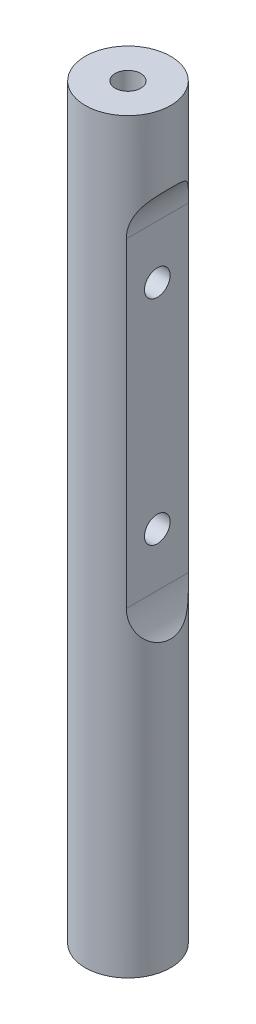
SolidWorks part; units mm, degrees
ref_plane "Front Plane" through (0, 0, 0) normal (0, 0, 1) x (1, 0, 0)
ref_plane "Top Plane" through (0, 0, 0) normal (0, 1, 0) x (1, 0, 0)
ref_plane "Right Plane" through (0, 0, 0) normal (1, 0, 0) x (0, 0, -1)
sketch "Sketch1" plane through (0, 0, 0) normal (0, 1, 0) x (1, 0, 0)
  circle A0 centre (0, 0) radius 5.08
  dimension "D1" = 10.16
extrude "Boss-Extrude1" add sketch "Sketch1" along normal blind 88.9
hole_wizard "Tapped Hole for #4-40 Helicoil1" positions "Sketch2" profile "Sketch4" tap size "#4-40" standard "Helicoil® Inch"
sketch "Sketch2" plane through (0, 88.9, 0) normal (0, 1, 0) x (1, 0, 0)
  point P0 (0, 0)
sketch "Sketch4" plane through (0, 88.9, 0) normal (1, 0, 0) x (0, 0, 1)
  line L0 (0, 0) -> (0, 9.0437)
  line L1 (0, 9.0437) -> (1.524, 8.128)
  line L2 (1.524, 8.128) -> (1.524, 0)
  line L5 (1.524, 0) -> (0, 0)
  line L10 (0, 9.0437) -> (-1.524, 8.128) construction
  line L11 (0, -6.35) -> (0, 107.95) construction
  dimension "Tap Drill Dia." = 3.048
  dimension "Tap Drill Depth" = 8.128
  dimension "Drill Angle" = 118
cosmetic thread "Hole Thread1" parameters "D1"=3.556, "D2"=3.7414
hole_wizard "Tapped Hole for #4-40 Helicoil2" positions "Sketch7" profile "Sketch6" tap size "#4-40" standard "Helicoil® Inch"
sketch "Sketch7" plane through (0, 0, 0) normal (0, -1, 0) x (-1, 0, 0)
  point P0 (0, 0)
sketch "Sketch6" plane through (0, 0, 0) normal (1, 0, 0) x (0, 0, -1)
  line L0 (0, 0) -> (0, 9.0437)
  line L1 (0, 9.0437) -> (1.524, 8.128)
  line L2 (1.524, 8.128) -> (1.524, 0)
  line L5 (1.524, 0) -> (0, 0)
  line L10 (0, 9.0437) -> (-1.524, 8.128) construction
  line L11 (0, -6.35) -> (0, 107.95) construction
  dimension "Tap Drill Dia." = 3.048
  dimension "Tap Drill Depth" = 8.128
  dimension "Drill Angle" = 118
cosmetic thread "Hole Thread2" parameters "D1"=3.556, "D2"=3.7414
sketch "Sketch8" plane through (0, 0, 0) normal (0, 0, 1) x (1, 0, 0)
  line L0 (3.4925, 76.2) -> (3.4925, 38.1)
  line L1 (-5.08, 0) -> (5.08, 0) construction
  line L2 (5.08, 0) -> (5.08, 88.9) construction
  line L3 (5.08, 33.8999) -> (5.08, 88.9)
  arc A0 (5.08, 80.4001) -> (3.4925, 76.2) centre (9.8425, 76.2) ccw
  arc A1 (3.4925, 38.1) -> (5.08, 33.8999) centre (9.8425, 38.1) ccw
  dimension "D4" = 12.7
  dimension "D5" = 12.7
  dimension "D1" = 38.1
  dimension "D2" = 38.1
  dimension "D3" = 1.5875
extrude "Cut-Extrude1" cut sketch "Sketch8" along normal through all both and the other way through all contours L0 A1 L3 A0 region at (4.3061, 57.15, 0)
sketch "Sketch9" plane through (3.4925, 0, 0) normal (1, 0, 0) x (0, 0, -1)
  line L0 (0, 76.2) -> (0, 38.1) construction
  line L1 (-3.689, 76.2) -> (3.689, 76.2) construction
  line L2 (-3.689, 38.1) -> (3.689, 38.1) construction
  line L3 (-3.689, 69.85) -> (3.689, 69.85) construction
  line L4 (-3.689, 76.2) -> (-3.689, 38.1) construction
  line L5 (3.689, 38.1) -> (3.689, 76.2) construction
  line L6 (-3.689, 44.45) -> (3.689, 44.45) construction
  dimension "D1" = 6.35
  dimension "D2" = 6.35
hole_wizard "Tapped Hole for #4-40 Helicoil3" positions "Sketch10" profile "Sketch11" tap size "#4-40" standard "Helicoil® Inch" end condition through all
sketch "Sketch10" plane through (3.4925, 0, 0) normal (1, 0, 0) x (0, 0, -1)
  point P0 (0, 69.85)
  point P2 (0, 44.45)
sketch "Sketch11" plane through (3.4925, 69.85, 0) normal (0, 1, 0) x (0, 0, -1)
  line L0 (0, 0) -> (0, 8.5725)
  line L1 (0, 8.5725) -> (1.524, 8.5725)
  line L2 (1.524, 8.5725) -> (1.524, 0)
  line L5 (1.524, 0) -> (0, 0)
  line L11 (0, -6.35) -> (0, 107.95) construction
  dimension "Thru Tap Drill Dia." = 3.048
  dimension "Thru Tap Drill Depth" = 8.5725
cosmetic thread "Hole Thread3" parameters "D1"=3.556, "D2"=3.7414
cosmetic thread "Hole Thread4" parameters "D1"=3.556, "D2"=3.7414
